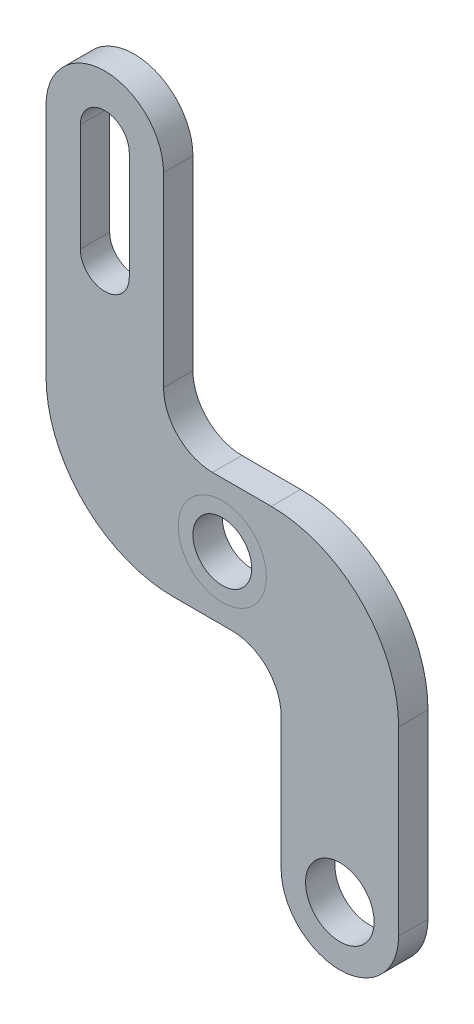
SolidWorks part; units mm, degrees
ref_plane "Front Plane" through (0, 0, 0) normal (0, 0, 1) x (1, 0, 0)
ref_plane "Top Plane" through (0, 0, 0) normal (0, 1, 0) x (1, 0, 0)
ref_plane "Right Plane" through (0, 0, 0) normal (1, 0, 0) x (0, 0, -1)
sketch "Sketch1" plane through (0, 0, 0) normal (0, 0, 1) x (1, 0, 0)
  line L0 (0, 0) -> (-7361.9261, 0) construction
  line L1 (0, 0) -> (0, -7361.9261) construction
  line L2 (-1, 6.5) -> (5, 6.5)
  line L3 (1, -6.5) -> (-5, -6.5)
  line L4 (-18, 6.5) -> (-18, 30.5)
  line L5 (-6, 30.5) -> (-6, 11.5)
  line L6 (18, -6.5) -> (18, -25)
  line L7 (6, -11.5) -> (6, -25)
  line L8 (-12, 30.5) -> (-12, 19.5) construction
  line L9 (-9.5, 30.5) -> (-9.5, 19.5)
  line L10 (-14.5, 30.5) -> (-14.5, 19.5)
  circle A0 centre (0, 0) radius 3
  circle A1 centre (0, 0) radius 4.5
  arc A2 (-5, -6.5) -> (-18, 6.5) centre (-5, 6.5) cw
  arc A3 (-6, 11.5) -> (-1, 6.5) centre (-1, 11.5) ccw
  arc A4 (5, 6.5) -> (18, -6.5) centre (5, -6.5) cw
  arc A5 (1, -6.5) -> (6, -11.5) centre (1, -11.5) cw
  arc A6 (-18, 30.5) -> (-6, 30.5) centre (-12, 30.5) cw
  arc A7 (18, -25) -> (6, -25) centre (12, -25) cw
  arc A8 (-9.5, 30.5) -> (-14.5, 30.5) centre (-12, 30.5) ccw
  arc A9 (-14.5, 19.5) -> (-9.5, 19.5) centre (-12, 19.5) ccw
  circle A10 centre (12, -25) radius 3.5
  point P27 (-12, 25)
  dimension "D1" = 6
  dimension "D2" = 9
  dimension "D3" = 13
  dimension "D4" = 13
  dimension "D5" = 5
  dimension "D6" = 5
  dimension "D12" = 6
  dimension "D13" = 6
  dimension "D14" = 7
  dimension "D7" = 25
  dimension "D8" = 19.5
  dimension "D9" = 11
  dimension "D10" = 6.5
  dimension "6.5" = 6.5
  dimension "D11" = 5
  dimension "D15" = 18
  dimension "D16" = 36
extrude "Boss-Extrude1" add sketch "Sketch1" along normal mid plane 3 contours A7 L6 A4 L2 A3 L5 A6 L4 A2 L3 A5 L7 A10 A9 L10 A8 L9 A1 region at (2, 5.735, 0)
extrude "Boss-Extrude2" add sketch "Sketch1<4>" along normal mid plane 3 separate body contours A1 A0 region at (-4.3727, 0, 0)
sketch "Sketch1<4>" plane through (0, 0, 0) normal (0, 0, 1) x (1, 0, 0) same geometry as "Sketch1"
